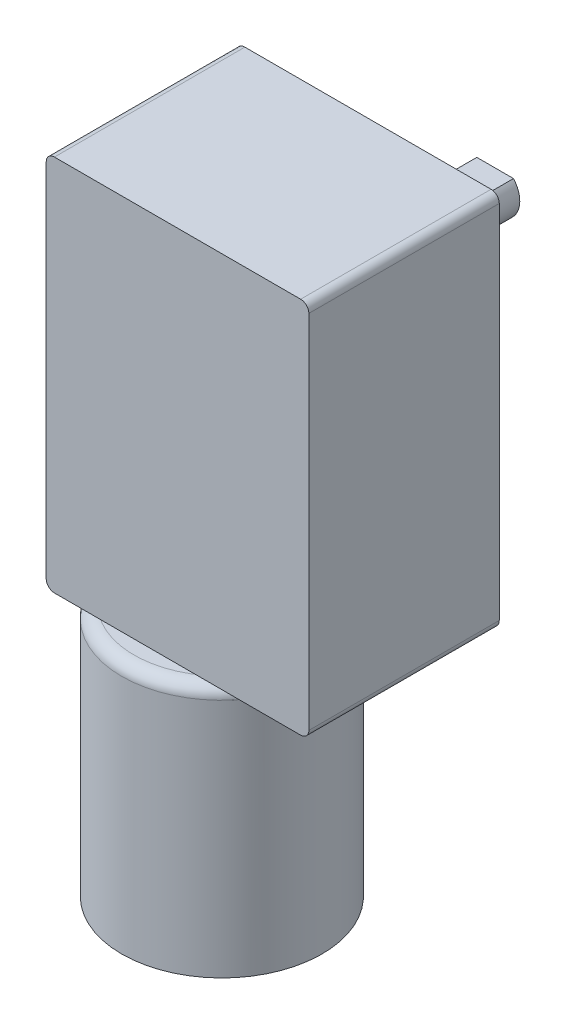
SolidWorks part; units mm, degrees
ref_plane "前视基准面" through (0, 0, 0) normal (0, 0, 1) x (1, 0, 0)
ref_plane "上视基准面" through (0, 0, 0) normal (0, 1, 0) x (1, 0, 0)
ref_plane "右视基准面" through (0, 0, 0) normal (1, 0, 0) x (0, 0, -1)
sketch "草图1" plane through (0, 0, 0) normal (0, 0, 1) x (1, 0, 0)
  line L1 (0, 0) -> (32, 0)
  line L2 (0, 0) -> (0, 46)
  line L3 (0, 46) -> (32, 46)
  line L4 (32, 0) -> (32, 46)
  circle A0 centre (7, 40) radius 3.7
  circle A1 centre (25, 40) radius 3.7
  circle A2 centre (7, 7) radius 3.7
  circle A3 centre (25, 7) radius 3.7
  point P13 (16, 46)
  dimension "D3" = 7.4
  dimension "D4" = 7.4
  dimension "D5" = 7.4
  dimension "D6" = 7.4
  dimension "D1" = 46
  dimension "D2" = 32
  dimension "D7" = 18
  dimension "D8" = 9
  dimension "D9" = 33
  dimension "D10" = 6
extrude "凸台-拉伸1" add sketch "草图1" along normal blind 23.2 contours A0 | A1 | A2 | A3 | L1 L4 L3 L2 A3 A2 A1 A0 region at (16, 22.9338, 0) region at (7, 40, 0) region at (25, 40, 0) region at (7, 7, 0) region at (25, 7, 0)
extrude "凸台-拉伸2" add sketch "草图1<3>" against normal blind 2 contours A0 | A1 | A2 | A3 region at (7, 40, 0) region at (25, 40, 0) region at (7, 7, 0) region at (25, 7, 0)
sketch "草图1<3>" plane through (0, 0, 0) normal (0, 0, 1) x (1, 0, 0) same geometry as "草图1"
hole_wizard "M3 螺纹孔1" positions "草图2" profile "草图3" tap size "M3" standard "GB"
sketch "草图2" plane through (0, 0, -2) normal (0, 0, -1) x (-1, 0, 0)
  point P0 (-7, 7)
  point P3 (-25, 7)
  point P6 (-25, 40)
  point P9 (-7, 40)
sketch "草图3" plane through (7, 7, -2) normal (1, 0, 0) x (0, 1, 0)
  line L0 (0, 0) -> (0, 8.2511)
  line L1 (0, 8.2511) -> (1.25, 7.5)
  line L2 (1.25, 7.5) -> (1.25, 0.275)
  line L3 (1.25, 0.275) -> (1.525, 0)
  line L5 (1.525, 0) -> (0, 0)
  line L6 (-1.25, 0.275) -> (-1.525, 0) construction
  line L10 (0, 8.2511) -> (-1.25, 7.5) construction
  line L11 (0, -6.35) -> (0, 107.95) construction
  dimension "螺纹孔钻头直径" = 2.5
  dimension "螺纹孔钻头深度" = 7.5
  dimension "近端锥形沉头孔直径" = 3.05
  dimension "近端锥形沉头孔角度" = 90
  dimension "导头角度" = 118
cosmetic thread "孔螺蚊线1" parameters "D1"=6, "D2"=3
cosmetic thread "孔螺蚊线2" parameters "D1"=6, "D2"=3
cosmetic thread "孔螺蚊线3" parameters "D1"=6, "D2"=3
cosmetic thread "孔螺蚊线4" parameters "D1"=6, "D2"=3
sketch "草图4" plane through (0, 0, 0) normal (0, 0, -1) x (-1, 0, 0)
  line L0 (0, 46) -> (-32, 46) construction
  line L1 (-32, 0) -> (-32, 46) construction
  circle A0 centre (-16, 31) radius 3
  dimension "D3" = 6
  dimension "D1" = 15
  dimension "D2" = 16
extrude "凸台-拉伸3" add sketch "草图4" along normal blind 15.5
sketch "草图5" plane through (0, 0, 0) normal (0, 0, -1) x (-1, 0, 0)
  circle A0 centre (-16, 31) radius 7
  dimension "D1" = 14
extrude "凸台-拉伸4" add sketch "草图5" along normal blind 2
hole_wizard "M3 螺纹孔2" positions "草图6" profile "草图7" tap size "M3" standard "GB"
sketch "草图6" plane through (0, 0, -15.5) normal (0, 0, -1) x (-1, 0, 0)
  point P0 (-16, 31)
sketch "草图7" plane through (16, 31, -15.5) normal (1, 0, 0) x (0, 1, 0)
  line L0 (0, 0) -> (0, 14.7511)
  line L1 (0, 14.7511) -> (1.25, 14)
  line L2 (1.25, 14) -> (1.25, 0.275)
  line L3 (1.25, 0.275) -> (1.525, 0)
  line L5 (1.525, 0) -> (0, 0)
  line L6 (-1.25, 0.275) -> (-1.525, 0) construction
  line L10 (0, 14.7511) -> (-1.25, 14) construction
  line L11 (0, -6.35) -> (0, 107.95) construction
  dimension "螺纹孔钻头直径" = 2.5
  dimension "螺纹孔钻头深度" = 14
  dimension "近端锥形沉头孔直径" = 3.05
  dimension "近端锥形沉头孔角度" = 90
  dimension "导头角度" = 118
cosmetic thread "孔螺蚊线5" parameters "D1"=12, "D2"=3
sketch "草图8" plane through (0, 0, -15.5) normal (0, 0, -1) x (-1, 0, 0)
  line L0 (-18.2361, 33) -> (-13.7639, 33)
  arc A0 (-13.7639, 33) -> (-18.2361, 33) centre (-16, 31) ccw
  dimension "D1" = 6
  dimension "D2" = 2
extrude "切除-拉伸1" cut sketch "草图8" against normal blind 12
fillet "圆角1" radius 1 4 edges at (0, 46, 11.6) (0, 0, 11.6) (32, 46, 11.6) (32, 0, 11.6)
ref_plane "基准面1" through (0, -0.2, 0) normal (0, -1, 0) x (-1, 0, 0)
sketch "草图11" plane through (0, -0.2, 0) normal (0, -1, 0) x (-1, 0, 0)
  line L0 (-1, 0) -> (-31, 0) construction
  line L1 (0, 0) -> (0, -23.2) construction
  circle A0 centre (-12.2, -14) radius 12.2
  dimension "D1" = 24.4
  dimension "D2" = 14
extrude "凸台-拉伸6" add sketch "草图11" along normal blind 30.8 separate body
fillet "圆角2" radius 1.5 1 edges at (12.2, -0.2, 1.8)
sketch "草图12" plane through (0, -31, 0) normal (0, -1, 0) x (1, 0, 0)
  circle A0 centre (12.2, 14) radius 3.25
  dimension "D1" = 6.5
extrude "凸台-拉伸7" add sketch "草图12" along normal blind 2
